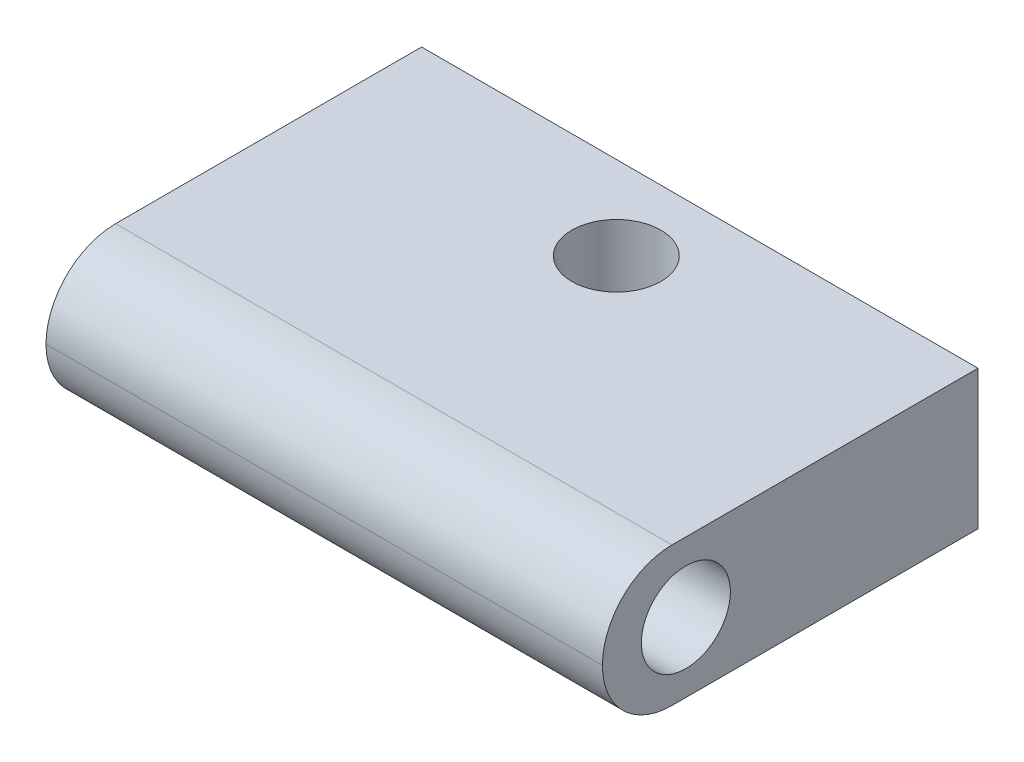
SolidWorks part; units mm, degrees
ref_plane "Front Plane" through (0, 0, 0) normal (0, 0, 1) x (1, 0, 0)
ref_plane "Top Plane" through (0, 0, 0) normal (0, 1, 0) x (1, 0, 0)
ref_plane "Right Plane" through (0, 0, 0) normal (1, 0, 0) x (0, 0, -1)
sketch "Sketch1" plane through (0, 0, 0) normal (0, 1, 0) x (1, 0, 0)
  line L2 (-10, 6.75) -> (-10, -6.75)
  line L3 (-10, -6.75) -> (10, -6.75)
  line L4 (10, 6.75) -> (10, -6.75)
  line L7 (10, 6.75) -> (-10, 6.75)
  point P3 (10, 0)
  point P4 (0, -6.75)
  dimension "D1" = 13.5
  dimension "D2" = 20
extrude "Boss-Extrude1" add sketch "Sketch1" along normal blind 5
sketch "Sketch2" plane through (0, 5, 0) normal (0, 1, 0) x (1, 0, 0)
  line L3 (10, 6.75) -> (-10, 6.75) construction
  point P0 (0, 3.75)
  dimension "D1" = 3
hole_wizard "Ø3.2 (3.2) M2 heat set" positions "Sketch2" profile "Sketch3" hole size "Ø3.2" standard "ANSI Metric" end condition up to next
sketch "Sketch3" plane through (0, 5, -3.75) normal (1, 0, 0) x (0, 0, 1)
  line L0 (0, 0) -> (0, 5)
  line L1 (0, 5) -> (1.6, 5)
  line L2 (1.6, 5) -> (1.6, 0)
  line L5 (1.6, 0) -> (0, 0)
  line L11 (0, -6.35) -> (0, 107.95) construction
  dimension "Thru Hole Dia." = 3.2
  dimension "Thru Hole Depth" = 5
sketch "Sketch4" [suppressed] plane through (0, 0, 0) normal (0, 1, 0) x (1, 0, 0)
  point P0 (0, 3.75)
hole_wizard "CBORE for M2 SHCS1" [suppressed] positions "Sketch4" profile "Sketch5" counterbore size "M2" standard "ANSI Metric"
sketch "Sketch5" plane through (0, 0, -3.75) normal (1, 0, 0) x (0, 0, -1)
  line L0 (0, 0) -> (0, 5)
  line L1 (0, 5) -> (1.2, 5)
  line L3 (1.2, 5) -> (1.2, 2)
  line L4 (1.2, 2) -> (2.2, 2)
  line L5 (2.2, 2) -> (2.2, 0)
  line L7 (2.2, 0) -> (0, 0)
  line L11 (0, -6.35) -> (0, 107.95) construction
  dimension "Thru Hole Dia." = 2.4
  dimension "Thru Hole Depth" = 5
  dimension "C'Bore Dia." = 4.4
  dimension "C'Bore Depth" = 2
fillet "Fillet2" radius 2.5 2 edges at (0, 0, 6.75) (0, 5, 6.75)
hole_wizard "Ø3.2 (3.2) Diameter Hole1" positions "Sketch6" profile "Sketch7" hole size "Ø3.2" standard "ANSI Metric" end condition up to next
sketch "Sketch6" plane through (10, 0, 0) normal (1, 0, 0) x (0, 0, -1)
  point P0 (-3.75, 2.5)
  dimension "D1" = 3
sketch "Sketch7" plane through (10, 2.5, 3.75) normal (0, 1, 0) x (0, 0, -1)
  line L0 (0, 0) -> (0, 20)
  line L1 (0, 20) -> (1.6, 20)
  line L2 (1.6, 20) -> (1.6, 0)
  line L5 (1.6, 0) -> (0, 0)
  line L11 (0, -6.35) -> (0, 107.95) construction
  dimension "Thru Hole Dia." = 3.2
  dimension "Thru Hole Depth" = 20
